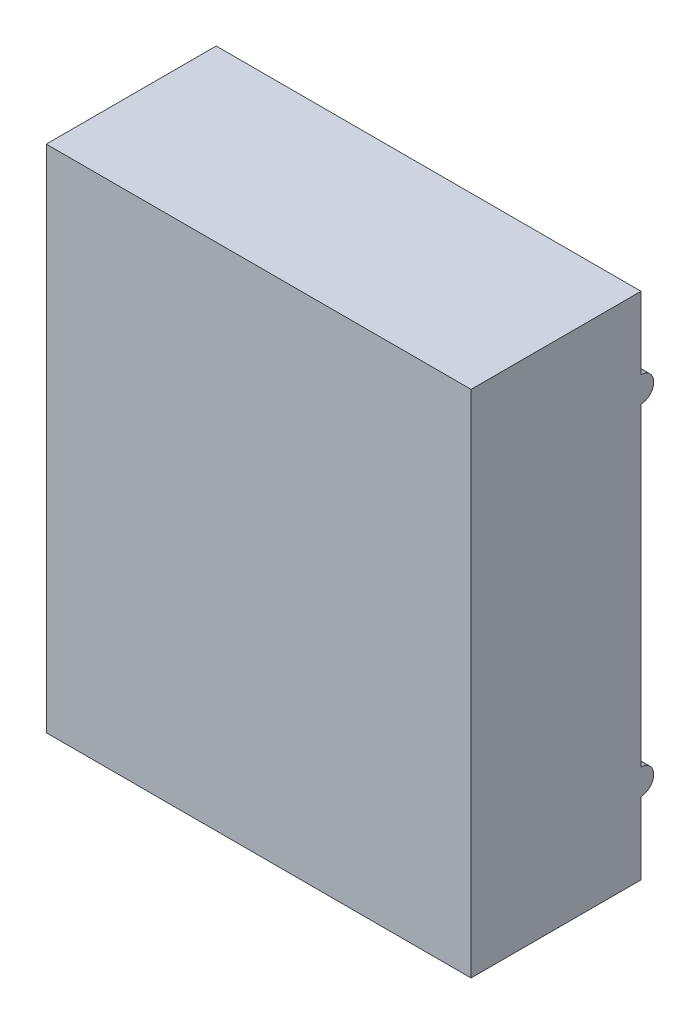
SolidWorks part; units mm, degrees
ref_plane "Front Plane" through (0, 0, 0) normal (0, 0, 1) x (1, 0, 0)
ref_plane "Top Plane" through (0, 0, 0) normal (0, 1, 0) x (1, 0, 0)
ref_plane "Right Plane" through (0, 0, 0) normal (1, 0, 0) x (0, 0, -1)
other "Center of Mass"
sketch "Sketch1" plane through (0, 0, 0) normal (0, 0, 1) x (1, 0, 0)
  line L1 (-125, -150) -> (125, -150)
  line L2 (-125, -150) -> (-125, 150)
  line L3 (-125, 150) -> (125, 150)
  line L4 (125, -150) -> (125, 150)
  line L5 (-125, -150) -> (125, 150) construction
  line L6 (-125, 150) -> (125, -150) construction
  point P0 (0, 0)
  dimension "D1" = 300
  dimension "D2" = 250
extrude "Boss-Extrude1" add sketch "Sketch1" along normal blind 100
sketch "Sketch2" plane through (0, 0, 0) normal (0, 0, -1) x (-1, 0, 0)
  line L0 (0, -100) -> (0, 100)
  line L1 (7.5, 92.5) -> (-7.5, 92.5)
  line L2 (7.5, 92.5) -> (7.5, 107.5)
  line L3 (7.5, 107.5) -> (-7.5, 107.5)
  line L4 (-7.5, 92.5) -> (-7.5, 107.5)
  line L5 (7.5, 92.5) -> (-7.5, 107.5) construction
  line L6 (7.5, 107.5) -> (-7.5, 92.5) construction
  line L7 (7.5, -107.5) -> (-7.5, -107.5)
  line L8 (7.5, -107.5) -> (7.5, -92.5)
  line L9 (7.5, -92.5) -> (-7.5, -92.5)
  line L10 (-7.5, -107.5) -> (-7.5, -92.5)
  line L11 (7.5, -107.5) -> (-7.5, -92.5) construction
  line L12 (7.5, -92.5) -> (-7.5, -107.5) construction
  point P0 (0, 100)
  point P5 (0, -100)
  point P14 (0, 0)
  dimension "D1" = 15
  dimension "D2" = 200
extrude "Boss-Extrude2" add sketch "Sketch2" along normal blind 7.5 contours L10 L7 L8 L9 | L4 L1 L2 L3 region at (3.75, 92.7121, 0) region at (-3.75, -92.7121, 0)
fillet "Fillet1" radius 7.5 4 edges at (0, 107.5, -7.5) (0, 92.5, -7.5) (0, -107.5, -7.5) (0, -92.5, -7.5)
sketch "Sketch3" plane through (-125, 0, 0) normal (-1, 0, 0) x (0, 0, 1)
  line L0 (0, 92.5) -> (0, 107.5) construction
  circle A0 centre (0, 100) radius 7.5
  circle A1 centre (0, -100) radius 7.5
  dimension "D1" = 15
extrude "Boss-Extrude3" add sketch "Sketch3" against normal blind 10
sketch "Sketch4" plane through (125, 0, 0) normal (1, 0, 0) x (0, 0, -1)
  line L0 (0, -107.5) -> (0, -92.5) construction
  circle A0 centre (0, 100) radius 7.5
  circle A1 centre (0, -100) radius 7.5
  dimension "D1" = 15
extrude "Boss-Extrude4" add sketch "Sketch4" against normal blind 10
